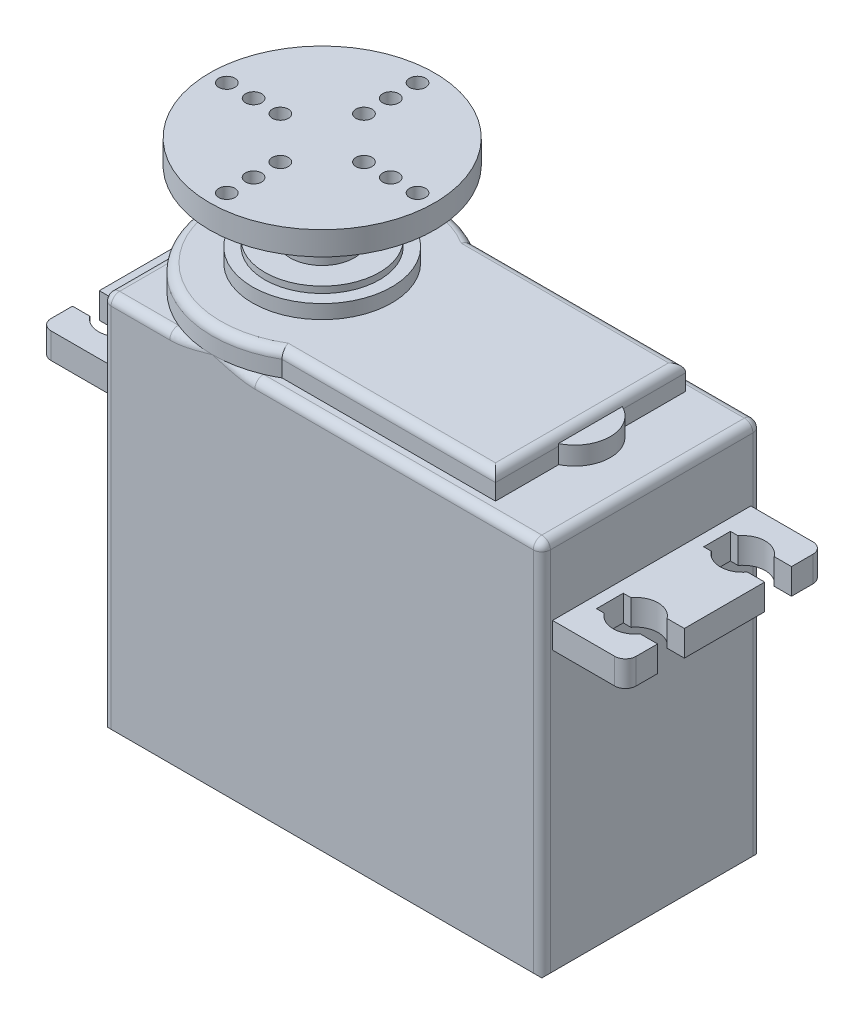
SolidWorks part; units mm, degrees
ref_plane "前视基准面" through (0, 0, 0) normal (0, 0, 1) x (1, 0, 0)
ref_plane "上视基准面" through (0, 0, 0) normal (0, 1, 0) x (1, 0, 0)
ref_plane "右视基准面" through (0, 0, 0) normal (1, 0, 0) x (0, 0, -1)
sketch "草图2" plane through (0, 0, 0) normal (0, 1, 0) x (1, 0, 0)
  line L1 (-20.5, 10.25) -> (20.5, 10.25)
  line L2 (-20.5, 10.25) -> (-20.5, -10.25)
  line L3 (-20.5, -10.25) -> (20.5, -10.25)
  line L4 (20.5, 10.25) -> (20.5, -10.25)
  line L5 (0, -10.25) -> (0, 10.25) construction
  line L6 (-20.5, 0) -> (20.5, 0) construction
  point P0 (0, 0)
  dimension "D1" = 41
  dimension "D2" = 20.5
extrude "凸台-拉伸1" add sketch "草图2" along normal blind 37
chamfer "倒角1" distance 2 angle 45 4 edges at (-20.5, 0, 0) (0, 0, -10.25) (20.5, 0, 0) (0, 0, 10.25)
sketch "草图3" plane through (0, 37, 0) normal (0, 1, 0) x (1, 0, 0)
  line L0 (-5.122, 8.875) -> (14.8, 8.875)
  line L1 (14.8, 8.875) -> (14.8, 2.9719)
  line L2 (14.8, -8.875) -> (-5.122, -8.875)
  line L3 (0, 0) -> (24.9336, 0) construction
  line L4 (20.5, 10.25) -> (-20.5, 10.25) construction
  line L5 (-20.5, 10.25) -> (-20.5, -10.25) construction
  line L6 (-20.5, -10.25) -> (20.5, -10.25) construction
  line L7 (20.5, -10.25) -> (20.5, 10.25) construction
  line L8 (14.8, -2.9719) -> (14.8, -8.875)
  arc A0 (-5.122, 8.875) -> (-5.122, -8.875) centre (-10.25, 0) ccw
  arc A1 (14.8, -2.9719) -> (14.8, 2.9719) centre (13.32, 0) ccw
  dimension "D2" = 6.64
  dimension "D3" = 1.48
  dimension "D1" = 17.75
  dimension "D4" = 5.7
extrude "凸台-拉伸2" add sketch "草图3" along normal blind 2.3
sketch "草图4" plane through (0, 39.3, 0) normal (0, 1, 0) x (1, 0, 0)
  line L0 (14.8, 2.9719) -> (14.8, -2.9719)
  arc A0 (14.8, -2.9719) -> (14.8, 2.9719) centre (13.32, 0) ccw construction
  arc A1 (14.8, -2.9719) -> (14.8, 2.9719) centre (13.32, 0) ccw
extrude "切除-拉伸1" cut sketch "草图4" against normal blind 0.6
sketch "草图5" plane through (0, 39.3, 0) normal (0, 1, 0) x (1, 0, 0)
  circle A0 centre (-10.25, 0) radius 6.5
  dimension "D1" = 13
extrude "凸台-拉伸3" add sketch "草图5" along normal blind 1.3
sketch "草图6" plane through (0, 40.6, 0) normal (0, 1, 0) x (1, 0, 0)
  circle A0 centre (-10.25, 0) radius 5.35
  dimension "D1" = 10.7
extrude "凸台-拉伸4" add sketch "草图6" along normal blind 0.6
sketch "草图7" plane through (0, 41.2, 0) normal (0, 1, 0) x (1, 0, 0)
  circle A0 centre (-10.25, 0) radius 3
  dimension "D1" = 6
extrude "凸台-拉伸5" add sketch "草图7" along normal blind 6
sketch "草图8" plane through (0, 47.2, 0) normal (0, 1, 0) x (1, 0, 0)
  circle A0 centre (-10.25, 0) radius 10.5
  point P5 (-10.25, 0)
  dimension "D1" = 21
extrude "凸台-拉伸6" add sketch "草图8" along normal blind 2.2
sketch "草图9" plane through (0, 49.4, 0) normal (0, 1, 0) x (1, 0, 0)
  line L1 (-10.25, 0) -> (-20.75, 0) construction
  circle A2 centre (-14.15, 0) radius 0.75
  circle A3 centre (-10.25, 0) radius 10.5 construction
  circle A4 centre (-16.65, 0) radius 0.75
  circle A5 centre (-19.15, 0) radius 0.75
  dimension "D1" = 1.5
  dimension "D2" = 2.5
  dimension "D5" = 1.5
  dimension "D6" = 1.5
  dimension "D3" = 2.5
  dimension "D4" = 3.9
extrude "切除-拉伸2" cut sketch "草图9" against normal up to next
pattern_circular "阵列(圆周)1" count 4 over 360 about axis through (-10.25, 49.4, 0) along (0, 1, 0) of "切除-拉伸2"
fillet "圆角1" radius 0.8 4 edges at (20.5, 19.5, -10.25) (-20.5, 19.5, -10.25) (20.5, 19.5, 10.25) (-20.5, 19.5, 10.25)
fillet "圆角2" radius 0.8 15 edges at (-20.2657, 37, -10.0157) (-14.975, 37, -10.25) (4.725, 37, -10.25) (20.2657, 37, -10.0157) (20.5, 37, 0) (20.2657, 37, 10.0157) (4.725, 37, 10.25) (-14.975, 37, 10.25) (-20.2657, 37, 10.0157) (-20.5, 37, 4.725) (-20.5, 37, -4.725) (14.8, 39.3, 0) (4.839, 39.3, -8.875) (4.839, 39.3, 8.875) (-20.5, 39.3, 0)
sketch "草图15" plane through (-20.5, 0, 0) normal (-1, 0, 0) x (0, 0, 1)
  line L0 (9.45, 36.2) -> (3.9699, 36.2) construction
  line L1 (-9.25, 30.4) -> (9.25, 30.4)
  line L2 (-9.25, 30.4) -> (-9.25, 28)
  line L3 (-9.25, 28) -> (9.25, 28)
  line L4 (9.25, 30.4) -> (9.25, 28)
  line L5 (0, 28) -> (0, 30.4) construction
  line L6 (-9.25, 29.2) -> (9.25, 29.2) construction
  line L7 (-10.25, 2) -> (-10.25, 36.2) construction
  point P0 (0, 29.2)
  dimension "D1" = 18.5
  dimension "D2" = 2.4
  dimension "D3" = 5.8
  dimension "D4" = 1
extrude "凸台-拉伸10" add sketch "草图15" along normal blind 6.8
fillet "圆角3" radius 1 2 edges at (-27.3, 29.2, -9.25) (-27.3, 29.2, 9.25)
sketch "草图16" plane through (0, 30.4, 0) normal (0, 1, 0) x (1, 0, 0)
  line L0 (-27.3, 0) -> (-19.7, 0) construction
  line L1 (-27.3, -8.25) -> (-27.3, 8.25) construction
  line L2 (-22.3125, 3.75) -> (-21.6, 3.75)
  line L3 (-27.3, 6.25) -> (-25.6875, 6.25)
  line L4 (-27.3, 6.25) -> (-27.3, 3.75)
  line L5 (-27.3, 3.75) -> (-25.6875, 3.75)
  line L6 (-21.6, 6.25) -> (-21.6, 3.75)
  line L7 (-22.3125, 6.25) -> (-21.6, 6.25)
  line L8 (-27.3, 5) -> (-21.6, 5) construction
  line L9 (-27.3, -6.25) -> (-25.6875, -6.25)
  line L10 (-27.3, -6.25) -> (-27.3, -3.75)
  line L11 (-27.3, -3.75) -> (-25.6875, -3.75)
  line L12 (-22.3125, -3.75) -> (-21.6, -3.75)
  line L13 (-21.6, -6.25) -> (-21.6, -3.75)
  line L14 (-22.3125, -6.25) -> (-21.6, -6.25)
  arc A0 (-5.3411, 8.075) -> (-5.3411, -8.075) centre (-10.25, 0) ccw construction
  arc A1 (-25.6875, 3.75) -> (-22.3125, 3.75) centre (-24, 5) ccw
  arc A2 (-22.3125, 6.25) -> (-25.6875, 6.25) centre (-24, 5) ccw
  arc A3 (-25.6875, -3.75) -> (-22.3125, -3.75) centre (-24, -5) cw
  arc A4 (-22.3125, -6.25) -> (-25.6875, -6.25) centre (-24, -5) cw
  point P7 (-24.45, 5)
  dimension "D2" = 4.2
  dimension "D3" = 3.3
  dimension "D1" = 2.5
  dimension "D4" = 5.7
  dimension "D5" = 5
  dimension "D6" = 0
extrude "切除-拉伸3" cut sketch "草图16" against normal up to next
ref_plane "基准面4" through (0, 0, 0) normal (-1, 0, 0) x (0, 0, 1)
mirror "镜向1" about plane through (0, 0, 0) normal (-1, 0, 0) of "切除-拉伸3", "圆角3", "凸台-拉伸10"
